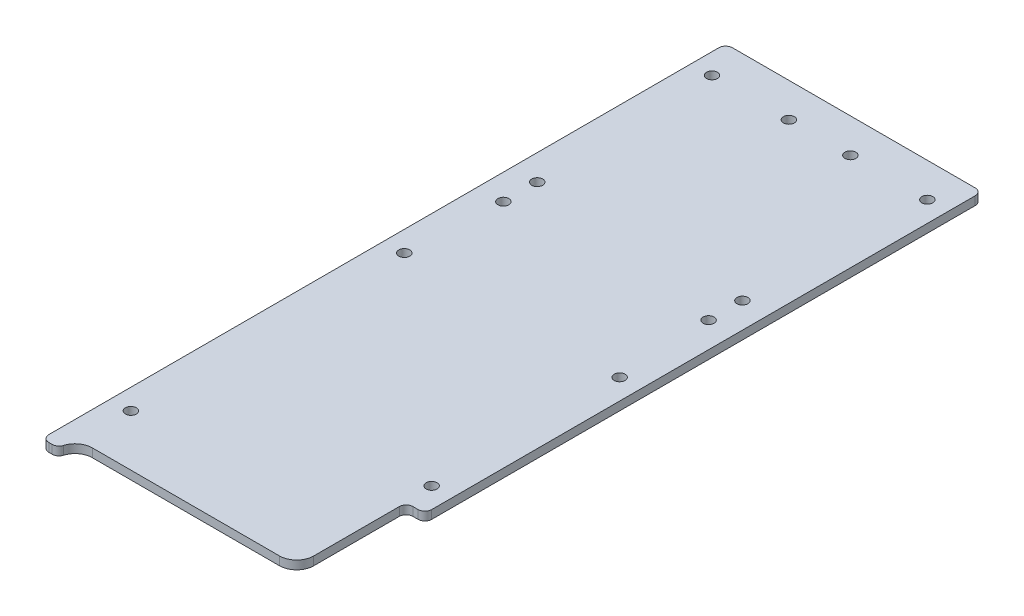
SolidWorks part; units mm, degrees
ref_plane "Front Plane" through (0, 0, 0) normal (0, 0, 1) x (1, 0, 0)
ref_plane "Top Plane" through (0, 0, 0) normal (0, 1, 0) x (1, 0, 0)
ref_plane "Right Plane" through (0, 0, 0) normal (1, 0, 0) x (0, 0, -1)
sketch "Sketch1" plane through (0, 0, 0) normal (0, 1, 0) x (1, 0, 0)
  line L0 (-39.9997, 0) -> (-39.9997, 114.3) construction
  line L1 (-47.625, 127) -> (47.625, 127)
  line L2 (-47.625, 127) -> (-47.625, -127)
  line L3 (-47.625, -127) -> (47.625, -127)
  line L4 (47.625, 127) -> (47.625, -127)
  line L5 (-47.625, 127) -> (47.625, -127) construction
  line L6 (-47.625, -127) -> (47.625, 127) construction
  line L7 (0, 0) -> (0, 127) construction
  line L8 (-39.9997, 0) -> (-39.9997, -101.6) construction
  line L9 (-39.9997, 0) -> (0, 0) construction
  line L10 (-41.275, -127) -> (-41.275, -120.65)
  line L11 (-41.275, -120.65) -> (41.275, -120.65)
  line L12 (41.275, -120.65) -> (41.275, -127)
  line L13 (-39.9997, 114.3) -> (-11.4247, 114.3) construction
  line L14 (39.9997, 114.3) -> (11.4247, 114.3) construction
  circle A0 centre (-39.9997, 114.3) radius 2.032
  circle A1 centre (-39.9997, 0) radius 2.032
  circle A2 centre (-39.9997, -101.6) radius 2.032
  circle A3 centre (39.9997, -101.6) radius 2.032
  circle A4 centre (39.9997, 0) radius 2.032
  circle A5 centre (39.9997, 114.3) radius 2.032
  circle A6 centre (-11.4247, 114.3) radius 2.032
  circle A7 centre (11.4247, 114.3) radius 2.032
  circle A8 centre (-39.9997, -69.85) radius 2.032
  circle A9 centre (39.9997, -69.85) radius 2.032
  point P0 (0, 0)
  dimension "D4" = 4.064
  dimension "D10" = 28.575
  dimension "D1" = 95.25
  dimension "D2" = 254
  dimension "D3" = 7.6253
  dimension "D5" = 12.7
  dimension "D6" = 25.4
  dimension "D7" = 6.35
  dimension "D8" = 6.35
  dimension "D9" = 6.35
  dimension "D11" = 69.85
extrude "Boss-Extrude1" add sketch "Sketch1" along normal blind 3.175 contours L4 L1 L2 L3 A4 A0 A1 A2 A3 A5 | A8 | A3 region at (0, 0, -2.6944) region at (39.9997, 0, 101.6) region at (-39.9997, 0, 69.85)
fillet "Fillet1" radius 2.54 4 edges at (-47.625, 1.5875, -127) (47.625, 1.5875, -127) (47.625, 1.5875, 127) (-47.625, 1.5875, 127)
fillet "Fillet2" radius 2.54 2 edges at (41.275, 1.5875, 127) (-41.275, 1.5875, 127)
fillet "Fillet3" radius 6.35 2 edges at (41.275, 1.5875, 120.65) (-41.275, 1.5875, 120.65)
sketch "Sketch2" plane through (0, 0, 0) normal (0, -1, 0) x (1, 0, 0)
  line L0 (41.91, 131.8831) -> (41.91, 109.8659) construction
  line L1 (41.91, 109.8659) -> (41.91, 106.3879) construction
  line L2 (41.91, 83.271) -> (41.91, 82.5325) construction
  line L3 (41.91, 82.5325) -> (41.91, 81.2514) construction
  line L4 (41.91, 83.271) -> (41.91, 106.3879) construction
  line L5 (41.91, 131.8831) -> (41.91, 109.8659)
  line L6 (41.91, 109.8659) -> (41.91, 106.3879)
  line L7 (41.91, 83.271) -> (41.91, 82.5325)
  line L8 (41.91, 82.5325) -> (41.91, 81.2514)
  line L9 (41.91, 83.271) -> (41.91, 106.3879)
  line L10 (41.91, 81.2514) -> (47.625, 81.2514)
  line L11 (47.625, -124.46) -> (47.625, 124.46) construction
  line L12 (41.91, 131.8831) -> (47.625, 131.8831)
  line L13 (47.625, 131.8831) -> (47.625, 81.2514)
  line L14 (40.64, 79.9814) -> (48.895, 79.9814)
  line L15 (48.895, 133.1531) -> (48.895, 79.9814)
  line L16 (40.64, 133.1531) -> (48.895, 133.1531)
  line L17 (40.64, 133.1531) -> (40.64, 109.8659)
  line L18 (40.64, 109.8659) -> (40.64, 106.3879)
  line L19 (40.64, 83.271) -> (40.64, 106.3879)
  line L20 (40.64, 83.271) -> (40.64, 82.5325)
  line L21 (40.64, 82.5325) -> (40.64, 79.9814)
  arc M7 (43.815, 127) -> (41.3809, 125.1857) centre (43.815, 124.46) ccw
  arc M8 (41.3809, 125.1857) -> (35.2956, 120.65) centre (35.2956, 127) cw
  line M18 (47.625, -124.46) -> (47.625, 124.46)
  dimension "D1" = 1.27
extrude "Cut-Extrude1" cut sketch "Sketch2" against normal through all contours L20 L21 L14 L10 L8 L7 L9 L19 M18 | L19 L9 L6 L5 L17 L18 M7 M8 | L13 L10 L8 L7 L9 L6 L5 L12 region at (41.6752, 0, 99.9787)
fillet "Fillet4" radius 6.35 1 edges at (40.64, 1.5875, 123.5708)
fillet "Fillet5" radius 2.54 2 edges at (47.625, 1.5875, 79.9814) (40.64, 1.5875, 79.9814)
sketch "Sketch3" plane through (0, 0, 0) normal (0, -1, 0) x (1, 0, 0)
  line L0 (-36.3105, -49.7791) -> (-39.9173, -49.7791) construction
  line L1 (-40.4253, -49.276) -> (-40.4253, -45.7043) construction
  line L2 (-35.8025, -45.7043) -> (-35.8025, -49.276) construction
  line L3 (-39.9173, -45.2013) -> (-36.3105, -45.2013) construction
  line L4 (-36.3105, -37.2027) -> (-39.9173, -37.2027) construction
  line L5 (-35.8025, -33.1279) -> (-35.8025, -36.6996) construction
  line L6 (-40.4253, -36.6996) -> (-40.4253, -33.1279) construction
  line L7 (-39.9173, -32.6249) -> (-36.3105, -32.6249) construction
  line L8 (36.2827, -32.6249) -> (39.8895, -32.6249) construction
  line L9 (40.3975, -33.1279) -> (40.3975, -36.6996) construction
  line L10 (39.8895, -37.2027) -> (36.2827, -37.2027) construction
  line L11 (35.7747, -36.6996) -> (35.7747, -33.1279) construction
  line L12 (36.2827, -45.2013) -> (39.8895, -45.2013) construction
  line L13 (35.7747, -49.276) -> (35.7747, -45.7043) construction
  line L14 (40.3975, -45.7043) -> (40.3975, -49.276) construction
  line L15 (39.8895, -49.7791) -> (36.2827, -49.7791) construction
  line L16 (-36.3105, -49.7791) -> (-39.9173, -49.7791)
  line L17 (-40.4253, -49.276) -> (-40.4253, -45.7043)
  line L18 (-35.8025, -45.7043) -> (-35.8025, -49.276)
  line L19 (-39.9173, -45.2013) -> (-36.3105, -45.2013)
  line L20 (-36.3105, -37.2027) -> (-39.9173, -37.2027)
  line L21 (-35.8025, -33.1279) -> (-35.8025, -36.6996)
  line L22 (-40.4253, -36.6996) -> (-40.4253, -33.1279)
  line L23 (-39.9173, -32.6249) -> (-36.3105, -32.6249)
  line L24 (36.2827, -32.6249) -> (39.8895, -32.6249)
  line L25 (40.3975, -33.1279) -> (40.3975, -36.6996)
  line L26 (39.8895, -37.2027) -> (36.2827, -37.2027)
  line L27 (35.7747, -36.6996) -> (35.7747, -33.1279)
  line L28 (36.2827, -45.2013) -> (39.8895, -45.2013)
  line L29 (35.7747, -49.276) -> (35.7747, -45.7043)
  line L30 (40.3975, -45.7043) -> (40.3975, -49.276)
  line L31 (39.8895, -49.7791) -> (36.2827, -49.7791)
  line L32 (-47.625, -25.836) -> (47.625, -25.836)
  line L33 (-47.625, -124.46) -> (-47.625, 124.46) construction
  line L34 (47.625, -124.46) -> (47.625, 77.4414) construction
  line L35 (0, -25.836) -> (0, -56.0686) construction
  line L38 (134.3603, -51.414) -> (184.1361, -51.414)
  line L39 (184.1361, -51.414) -> (184.1361, -43.4909)
  line L40 (184.1361, -43.4909) -> (182.3327, -43.4909)
  line L41 (181.8247, -42.9878) -> (181.8247, -39.4161)
  line L42 (182.3327, -38.9131) -> (184.1361, -38.9131)
  line L43 (184.1361, -38.9131) -> (184.1361, -30.9899)
  line L44 (184.1361, -30.9899) -> (134.3603, -30.9899)
  line L45 (134.3603, -30.9899) -> (133.3361, -32.0042)
  line L46 (133.3361, -32.0042) -> (132.3119, -30.9899)
  line L47 (132.3119, -30.9899) -> (70.8603, -30.9899)
  line L48 (70.8603, -30.9899) -> (69.8361, -32.0042)
  line L49 (69.8361, -32.0042) -> (68.8119, -30.9899)
  line L50 (68.8119, -30.9899) -> (7.3603, -30.9899)
  line L51 (7.3603, -30.9899) -> (6.3361, -32.0042)
  line L52 (6.3361, -32.0042) -> (5.3119, -30.9899)
  line L53 (5.3119, -30.9899) -> (-56.1397, -30.9899)
  line L54 (-56.1397, -30.9899) -> (-57.1639, -32.0042)
  line L55 (-57.1639, -32.0042) -> (-58.1881, -30.9899)
  line L56 (-58.1881, -30.9899) -> (-119.6397, -30.9899)
  line L57 (-119.6397, -30.9899) -> (-120.6639, -32.0042)
  line L58 (-120.6639, -32.0042) -> (-121.6881, -30.9899)
  line L59 (-121.6881, -30.9899) -> (-184.1639, -30.9899)
  line L60 (-184.1639, -30.9899) -> (-184.1639, -51.414)
  line L61 (-184.1639, -51.414) -> (-121.6881, -51.414)
  line L62 (-121.6881, -51.414) -> (-120.6639, -50.3998)
  line L63 (-120.6639, -50.3998) -> (-119.6397, -51.414)
  line L64 (-119.6397, -51.414) -> (-58.1881, -51.414)
  line L65 (-58.1881, -51.414) -> (-57.1639, -50.3998)
  line L66 (-57.1639, -50.3998) -> (-56.1397, -51.414)
  line L67 (-56.1397, -51.414) -> (5.3119, -51.414)
  line L68 (5.3119, -51.414) -> (6.3361, -50.3998)
  line L69 (6.3361, -50.3998) -> (7.3603, -51.414)
  line L70 (7.3603, -51.414) -> (68.8119, -51.414)
  line L71 (68.8119, -51.414) -> (69.8361, -50.3998)
  line L72 (69.8361, -50.3998) -> (70.8603, -51.414)
  line L73 (70.8603, -51.414) -> (132.3119, -51.414)
  line L74 (132.3119, -51.414) -> (133.3361, -50.3998)
  line L75 (133.3361, -50.3998) -> (134.3603, -51.414)
  line L76 (134.3603, -51.414) -> (184.1361, -51.414)
  line L77 (184.1361, -51.414) -> (184.1361, -43.4909)
  line L78 (184.1361, -43.4909) -> (182.3327, -43.4909)
  line L79 (181.8247, -42.9878) -> (181.8247, -39.4161)
  line L80 (182.3327, -38.9131) -> (184.1361, -38.9131)
  line L81 (184.1361, -38.9131) -> (184.1361, -30.9899)
  line L82 (184.1361, -30.9899) -> (134.3603, -30.9899)
  line L83 (134.3603, -30.9899) -> (133.3361, -32.0042)
  line L84 (133.3361, -32.0042) -> (132.3119, -30.9899)
  line L85 (132.3119, -30.9899) -> (70.8603, -30.9899)
  line L86 (70.8603, -30.9899) -> (69.8361, -32.0042)
  line L87 (69.8361, -32.0042) -> (68.8119, -30.9899)
  line L88 (68.8119, -30.9899) -> (7.3603, -30.9899)
  line L89 (7.3603, -30.9899) -> (6.3361, -32.0042)
  line L90 (6.3361, -32.0042) -> (5.3119, -30.9899)
  line L91 (5.3119, -30.9899) -> (-56.1397, -30.9899)
  line L92 (-56.1397, -30.9899) -> (-57.1639, -32.0042)
  line L93 (-57.1639, -32.0042) -> (-58.1881, -30.9899)
  line L94 (-58.1881, -30.9899) -> (-119.6397, -30.9899)
  line L95 (-119.6397, -30.9899) -> (-120.6639, -32.0042)
  line L96 (-120.6639, -32.0042) -> (-121.6881, -30.9899)
  line L97 (-121.6881, -30.9899) -> (-184.1639, -30.9899)
  line L98 (-184.1639, -30.9899) -> (-184.1639, -51.414)
  line L99 (-184.1639, -51.414) -> (-121.6881, -51.414)
  line L100 (-121.6881, -51.414) -> (-120.6639, -50.3998)
  line L101 (-120.6639, -50.3998) -> (-119.6397, -51.414)
  line L102 (-119.6397, -51.414) -> (-58.1881, -51.414)
  line L103 (-58.1881, -51.414) -> (-57.1639, -50.3998)
  line L104 (-57.1639, -50.3998) -> (-56.1397, -51.414)
  line L105 (-56.1397, -51.414) -> (5.3119, -51.414)
  line L106 (5.3119, -51.414) -> (6.3361, -50.3998)
  line L107 (6.3361, -50.3998) -> (7.3603, -51.414)
  line L108 (7.3603, -51.414) -> (68.8119, -51.414)
  line L109 (68.8119, -51.414) -> (69.8361, -50.3998)
  line L110 (69.8361, -50.3998) -> (70.8603, -51.414)
  line L111 (70.8603, -51.414) -> (132.3119, -51.414)
  line L112 (132.3119, -51.414) -> (133.3361, -50.3998)
  line L113 (133.3361, -50.3998) -> (134.3603, -51.414)
  line L1362 (-40.4253, -34.9138) -> (-35.8025, -34.9138)
  line L1857 (-38.1139, -32.6249) -> (-38.1139, -37.2027)
  line L1858 (-38.1139, -45.2013) -> (-38.1139, -49.7791)
  line L1859 (-40.4253, -47.4902) -> (-35.8025, -47.4902)
  circle A0 centre (-38.1139, -34.9138) radius 2.032
  circle A1 centre (-38.1139, -47.4902) radius 2.032
  circle A2 centre (38.1139, -47.4902) radius 2.032
  circle A3 centre (38.1139, -34.9138) radius 2.032
  ellipse E0 centre (-39.9173, -45.7043) end of major axis (-39.4093, -45.7043) minor radius 0.5031 (-39.9173, -45.2013) -> (-40.4253, -45.7043) ccw construction
  ellipse E1 centre (-39.9173, -49.276) end of major axis (-39.4093, -49.276) minor radius 0.5031 (-40.4253, -49.276) -> (-39.9173, -49.7791) ccw construction
  ellipse E2 centre (182.3327, -42.9878) end of major axis (182.8407, -42.9878) minor radius 0.5031 (181.8247, -42.9878) -> (182.3327, -43.4909) ccw
  ellipse E3 centre (182.3327, -39.4161) end of major axis (182.8407, -39.4161) minor radius 0.5031 (182.3327, -38.9131) -> (181.8247, -39.4161) ccw
  ellipse E4 centre (182.3327, -42.9878) end of major axis (182.8407, -42.9878) minor radius 0.5031 (181.8247, -42.9878) -> (182.3327, -43.4909) ccw
  ellipse E5 centre (182.3327, -39.4161) end of major axis (182.8407, -39.4161) minor radius 0.5031 (182.3327, -38.9131) -> (181.8247, -39.4161) ccw
  ellipse E6 centre (-36.3105, -49.276) end of major axis (-35.8025, -49.276) minor radius 0.5031 (-36.3105, -49.7791) -> (-35.8025, -49.276) ccw construction
  ellipse E7 centre (-36.3105, -45.7043) end of major axis (-35.8025, -45.7043) minor radius 0.5031 (-35.8025, -45.7043) -> (-36.3105, -45.2013) ccw construction
  ellipse E8 centre (-39.9173, -36.6996) end of major axis (-39.4093, -36.6996) minor radius 0.5031 (-40.4253, -36.6996) -> (-39.9173, -37.2027) ccw construction
  ellipse E9 centre (-36.3105, -36.6996) end of major axis (-35.8025, -36.6996) minor radius 0.5031 (-36.3105, -37.2027) -> (-35.8025, -36.6996) ccw construction
  ellipse E10 centre (-36.3105, -33.1279) end of major axis (-35.8025, -33.1279) minor radius 0.5031 (-35.8025, -33.1279) -> (-36.3105, -32.6249) ccw construction
  ellipse E11 centre (-39.9173, -33.1279) end of major axis (-39.4093, -33.1279) minor radius 0.5031 (-39.9173, -32.6249) -> (-40.4253, -33.1279) ccw construction
  ellipse E12 centre (39.8895, -33.1279) end of major axis (40.3975, -33.1279) minor radius 0.5031 (40.3975, -33.1279) -> (39.8895, -32.6249) ccw construction
  ellipse E13 centre (36.2827, -33.1279) end of major axis (36.7907, -33.1279) minor radius 0.5031 (36.2827, -32.6249) -> (35.7747, -33.1279) ccw construction
  ellipse E14 centre (39.8895, -36.6996) end of major axis (40.3975, -36.6996) minor radius 0.5031 (39.8895, -37.2027) -> (40.3975, -36.6996) ccw construction
  ellipse E15 centre (36.2827, -36.6996) end of major axis (36.7907, -36.6996) minor radius 0.5031 (35.7747, -36.6996) -> (36.2827, -37.2027) ccw construction
  ellipse E16 centre (36.2827, -45.7043) end of major axis (36.7907, -45.7043) minor radius 0.5031 (36.2827, -45.2013) -> (35.7747, -45.7043) ccw construction
  ellipse E17 centre (36.2827, -49.276) end of major axis (36.7907, -49.276) minor radius 0.5031 (35.7747, -49.276) -> (36.2827, -49.7791) ccw construction
  ellipse E18 centre (39.8895, -45.7043) end of major axis (40.3975, -45.7043) minor radius 0.5031 (40.3975, -45.7043) -> (39.8895, -45.2013) ccw construction
  ellipse E19 centre (39.8895, -49.276) end of major axis (40.3975, -49.276) minor radius 0.5031 (39.8895, -49.7791) -> (40.3975, -49.276) ccw construction
  ellipse E20 centre (-39.9173, -45.7043) end of major axis (-39.4093, -45.7043) minor radius 0.5031 (-39.9173, -45.2013) -> (-40.4253, -45.7043) ccw
  ellipse E21 centre (-39.9173, -49.276) end of major axis (-39.4093, -49.276) minor radius 0.5031 (-40.4253, -49.276) -> (-39.9173, -49.7791) ccw
  ellipse E22 centre (-36.3105, -49.276) end of major axis (-35.8025, -49.276) minor radius 0.5031 (-36.3105, -49.7791) -> (-35.8025, -49.276) ccw
  ellipse E23 centre (-36.3105, -45.7043) end of major axis (-35.8025, -45.7043) minor radius 0.5031 (-35.8025, -45.7043) -> (-36.3105, -45.2013) ccw
  ellipse E24 centre (-39.9173, -36.6996) end of major axis (-39.4093, -36.6996) minor radius 0.5031 (-40.4253, -36.6996) -> (-39.9173, -37.2027) ccw
  ellipse E25 centre (-36.3105, -36.6996) end of major axis (-35.8025, -36.6996) minor radius 0.5031 (-36.3105, -37.2027) -> (-35.8025, -36.6996) ccw
  ellipse E26 centre (-36.3105, -33.1279) end of major axis (-35.8025, -33.1279) minor radius 0.5031 (-35.8025, -33.1279) -> (-36.3105, -32.6249) ccw
  ellipse E27 centre (-39.9173, -33.1279) end of major axis (-39.4093, -33.1279) minor radius 0.5031 (-39.9173, -32.6249) -> (-40.4253, -33.1279) ccw
  ellipse E28 centre (39.8895, -33.1279) end of major axis (40.3975, -33.1279) minor radius 0.5031 (40.3975, -33.1279) -> (39.8895, -32.6249) ccw
  ellipse E29 centre (36.2827, -33.1279) end of major axis (36.7907, -33.1279) minor radius 0.5031 (36.2827, -32.6249) -> (35.7747, -33.1279) ccw
  ellipse E30 centre (39.8895, -36.6996) end of major axis (40.3975, -36.6996) minor radius 0.5031 (39.8895, -37.2027) -> (40.3975, -36.6996) ccw
  ellipse E31 centre (36.2827, -36.6996) end of major axis (36.7907, -36.6996) minor radius 0.5031 (35.7747, -36.6996) -> (36.2827, -37.2027) ccw
  ellipse E32 centre (36.2827, -45.7043) end of major axis (36.7907, -45.7043) minor radius 0.5031 (36.2827, -45.2013) -> (35.7747, -45.7043) ccw
  ellipse E33 centre (36.2827, -49.276) end of major axis (36.7907, -49.276) minor radius 0.5031 (35.7747, -49.276) -> (36.2827, -49.7791) ccw
  ellipse E34 centre (39.8895, -45.7043) end of major axis (40.3975, -45.7043) minor radius 0.5031 (40.3975, -45.7043) -> (39.8895, -45.2013) ccw
  ellipse E35 centre (39.8895, -49.276) end of major axis (40.3975, -49.276) minor radius 0.5031 (39.8895, -49.7791) -> (40.3975, -49.276) ccw
  dimension "D2" = 4.064
  dimension "D1" = 0
extrude "Cut-Extrude2" cut sketch "Sketch3" against normal through all contours A0 | A1 | A2 | A3
